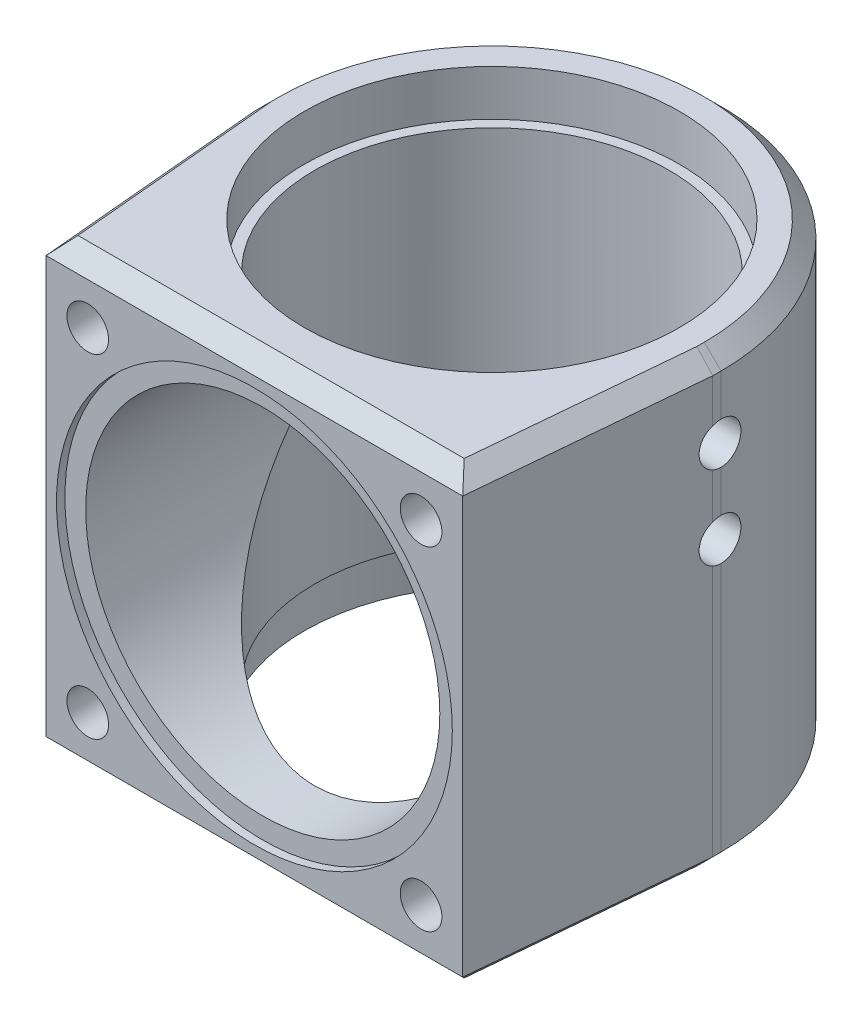
SolidWorks part; units mm, degrees
ref_plane "前视基准面" through (0, 0, 0) normal (0, 0, 1) x (1, 0, 0)
ref_plane "上视基准面" through (0, 0, 0) normal (0, 1, 0) x (1, 0, 0)
ref_plane "右视基准面" through (0, 0, 0) normal (1, 0, 0) x (0, 0, -1)
sketch "草图2" plane through (0, 0, 0) normal (0, 1, 0) x (1, 0, 0)
  line L0 (-50, 0) -> (50, 0)
  line L1 (55, 55) -> (55, 57)
  line L2 (-55, 55) -> (-55, 57)
  line L3 (-50, 0) -> (-55, 55)
  line L4 (50, 0) -> (55, 55)
  line L5 (0, -12.3445) -> (0, 139.9426) construction
  arc A0 (-55, 57) -> (55, 57) centre (0, 57) cw
  point P10 (0, 0)
  point P11 (0, 0)
  point P12 (0, 0)
  point P13 (0, 0)
  dimension "D1" = 57
  dimension "D2" = 110
  dimension "D3" = 5
  dimension "D5" = 55
  dimension "D6" = 100
extrude "凸台-拉伸2" add sketch "草图2" along normal blind 108
chamfer "倒角2" distance 4 angle 45 12 edges at (0, 0, 0) (52.5, 0, -27.5) (55, 0, -56) (0, 0, -112) (-55, 0, -56) (-52.5, 0, -27.5) (-55, 108, -56) (-52.5, 108, -27.5) (0, 108, 0) (52.5, 108, -27.5) (55, 108, -56) (0, 108, -112)
sketch "草图3" plane through (0, 108, 0) normal (0, 1, 0) x (1, 0, 0)
  circle A0 centre (0, 57) radius 42.5
  dimension "D1" = 85
extrude "切除-拉伸1" cut sketch "草图3" against normal through all
sketch "草图4" plane through (0, 108, 0) normal (0, 1, 0) x (1, 0, 0)
  circle A0 centre (0, 57) radius 45
  dimension "D1" = 90
extrude "切除-拉伸2" cut sketch "草图4" against normal blind 11
sketch "草图5" plane through (0, 0, 0) normal (0, -1, 0) x (1, 0, 0)
  circle A0 centre (0, -57) radius 45
  dimension "D1" = 90
extrude "切除-拉伸3" cut sketch "草图5" against normal blind 11
sketch "草图6" plane through (0, 0, 0) normal (0, 0, 1) x (1, 0, 0)
  line L0 (0, 4) -> (0, 104) construction
  line L1 (-50, 54) -> (50, 54) construction
  line L2 (-50, 104) -> (-50, 4) construction
  line L3 (50, 104) -> (50, 4) construction
  line L4 (0, 54) -> (50, 104) construction
  line L5 (50, 104) -> (-50, 104) construction
  line L6 (-50, 4) -> (50, 4) construction
  circle A0 centre (40, 94) radius 5
  circle A1 centre (-40, 94) radius 5
  circle A2 centre (-40, 14) radius 5
  circle A3 centre (40, 14) radius 5
  dimension "D2" = 10
  dimension "D1" = 80
extrude "切除-拉伸4" cut sketch "草图6" against normal blind 21
ref_plane "基准面4" through (0, 89, 0) normal (0, 1, 0) x (1, 0, 0)
ref_plane "基准面5" through (0, 69, 0) normal (0, 1, 0) x (1, 0, 0)
sketch "草图8" plane through (0, 89, 0) normal (0, 1, 0) x (1, 0, 0)
  line L0 (51, 57) -> (8.4625, 57) construction
  line L1 (55, 57) -> (25, 57)
  line L2 (25, 57) -> (25, 55)
  line L3 (25, 55) -> (45, 55)
  line L4 (45, 55) -> (45, 52)
  line L5 (45, 52) -> (55, 52)
  line L6 (55, 52) -> (55, 57)
  dimension "D1" = 5
  dimension "D2" = 2
  dimension "D3" = 10
  dimension "D4" = 20
revolve "切除-旋转2" cut sketch "草图8" angle 360 about L0
sketch "草图9" plane through (0, 69, 0) normal (0, 1, 0) x (1, 0, 0)
  line L6 (55, 57) -> (25, 57)
  line L7 (25, 57) -> (25, 55)
  line L8 (25, 55) -> (45, 55)
  line L9 (45, 55) -> (45, 52)
  line L10 (45, 52) -> (55, 52)
  line L11 (55, 52) -> (55, 57)
  line L12 (55, 57) -> (25, 57)
  line L13 (25, 57) -> (25, 55)
  line L14 (25, 55) -> (45, 55)
  line L15 (45, 55) -> (45, 52)
  line L16 (45, 52) -> (55, 52)
  line L17 (55, 52) -> (55, 57)
  dimension "D1" = 0
revolve "切除-旋转3" cut sketch "草图9" angle 360 about L12
sketch "草图10" plane through (0, 0, 0) normal (0, 0, 1) x (1, 0, 0)
  line L0 (0, 11) -> (0, 97) construction
  line L1 (0, 104) -> (0, 108) construction
  circle A0 centre (0, 54) radius 47.5
  point P6 (0, 0)
  dimension "D1" = 95
extrude "切除-拉伸5" cut sketch "草图10" against normal blind 2
sketch "草图11" plane through (0, 0, -2) normal (0, 0, 1) x (1, 0, 0)
  circle A0 centre (0, 54) radius 42.5
  dimension "D1" = 85
extrude "切除-拉伸6" cut sketch "草图11" against normal blind 55
